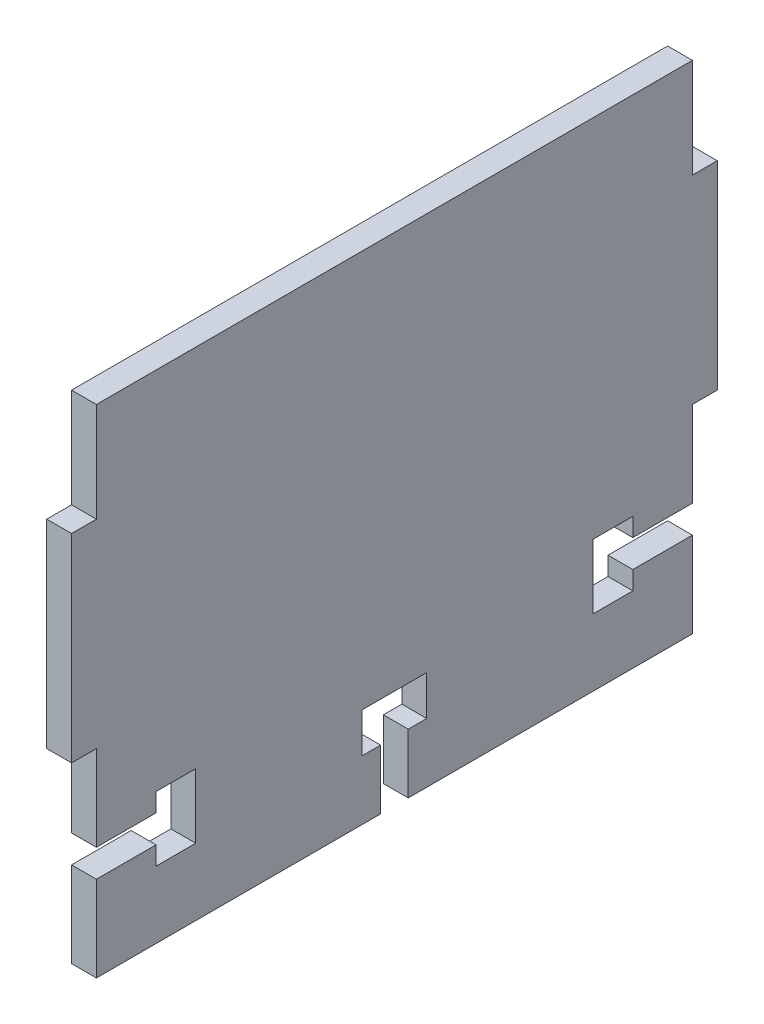
SolidWorks part; units mm, degrees
ref_plane "Front Plane" through (0, 0, 0) normal (0, 0, 1) x (1, 0, 0)
ref_plane "Top Plane" through (0, 0, 0) normal (0, 1, 0) x (1, 0, 0)
ref_plane "Right Plane" through (0, 0, 0) normal (1, 0, 0) x (0, 0, -1)
sketch "Sketch1" plane through (0, 0, 0) normal (1, 0, 0) x (0, 0, -1)
  line L0 (-4.1275, -19.05) -> (4.1275, -19.05)
  line L1 (-38.1, 31.75) -> (38.1, 31.75)
  line L2 (-38.1, 31.75) -> (-38.1, 19.05)
  line L3 (-38.1, -31.75) -> (-1.7653, -31.75)
  line L4 (38.1, 31.75) -> (38.1, 19.05)
  line L5 (4.1275, -24.13) -> (4.1275, -19.05)
  line L6 (1.7653, -24.13) -> (4.1275, -24.13)
  line L7 (-4.1275, -24.13) -> (-1.7653, -24.13)
  line L8 (-1.7653, -31.75) -> (-1.7653, -24.13)
  line L9 (1.7653, -31.75) -> (1.7653, -24.13)
  line L10 (-4.1275, -24.13) -> (-4.1275, -19.05)
  line L11 (14.4653, -31.75) -> (38.1, -31.75)
  line L12 (0, -34.389) -> (0, -15.9101) construction
  line L13 (10.9347, -31.75) -> (14.4653, -31.75)
  line L14 (-38.1, -19.05) -> (-20.5323, -19.05) construction
  line L15 (-38.1, -17.2847) -> (-30.48, -17.2847)
  line L16 (-38.1, -20.8153) -> (-38.1, -31.75)
  line L17 (-38.1, -20.8153) -> (-30.48, -20.8153)
  line L18 (38.1, -17.2847) -> (30.48, -17.2847)
  line L19 (-30.48, -20.8153) -> (-30.48, -23.1775)
  line L20 (1.7653, -31.75) -> (10.9347, -31.75)
  line L21 (-38.1, -6.35) -> (-38.1, -17.2847)
  line L23 (38.1, -6.35) -> (38.1, -17.2847)
  line L26 (-38.1, 19.05) -> (-41.275, 19.05)
  line L27 (-30.48, -14.9225) -> (-25.4, -14.9225)
  line L29 (-38.1, -6.35) -> (-41.275, -6.35)
  line L30 (-30.48, -14.9225) -> (-30.48, -17.2847)
  line L31 (-30.48, -23.1775) -> (-25.4, -23.1775)
  line L32 (-25.4, -14.9225) -> (-25.4, -23.1775)
  line L33 (30.48, -20.8153) -> (30.48, -23.1775)
  line L34 (38.1, -20.8153) -> (30.48, -20.8153)
  line L35 (30.48, -23.1775) -> (25.4, -23.1775)
  line L36 (25.4, -14.9225) -> (25.4, -23.1775)
  line L37 (30.48, -14.9225) -> (25.4, -14.9225)
  line L38 (30.48, -14.9225) -> (30.48, -17.2847)
  line L39 (38.1, -20.8153) -> (38.1, -31.75)
  line L40 (-41.275, 19.05) -> (-41.275, -6.35)
  line L41 (38.1, 19.05) -> (41.275, 19.05)
  line L43 (38.1, -6.35) -> (41.275, -6.35)
  line L44 (41.275, 19.05) -> (41.275, -6.35)
  dimension "D1" = 76.2
  dimension "D2" = 63.5
  dimension "D3" = 38.1
  dimension "D4" = 31.75
  dimension "D5" = 7.62
  dimension "D6" = 5.08
  dimension "D7" = 3.5306
  dimension "D8" = 8.255
  dimension "D9" = 1.7653
  dimension "D10" = 4.1275
  dimension "D11" = 38.1
  dimension "D13" = 25.4
  dimension "D14" = 25.4
  dimension "D15" = 3.175
  dimension "D16" = 3.175
  dimension "D12" = 12.7
  dimension "D17" = 3.5306
  dimension "D19" = 5.08
  dimension "D20" = 4.1275
  dimension "D21" = 8.255
extrude "Boss-Extrude1" add sketch "Sketch1" along normal blind 3.175
